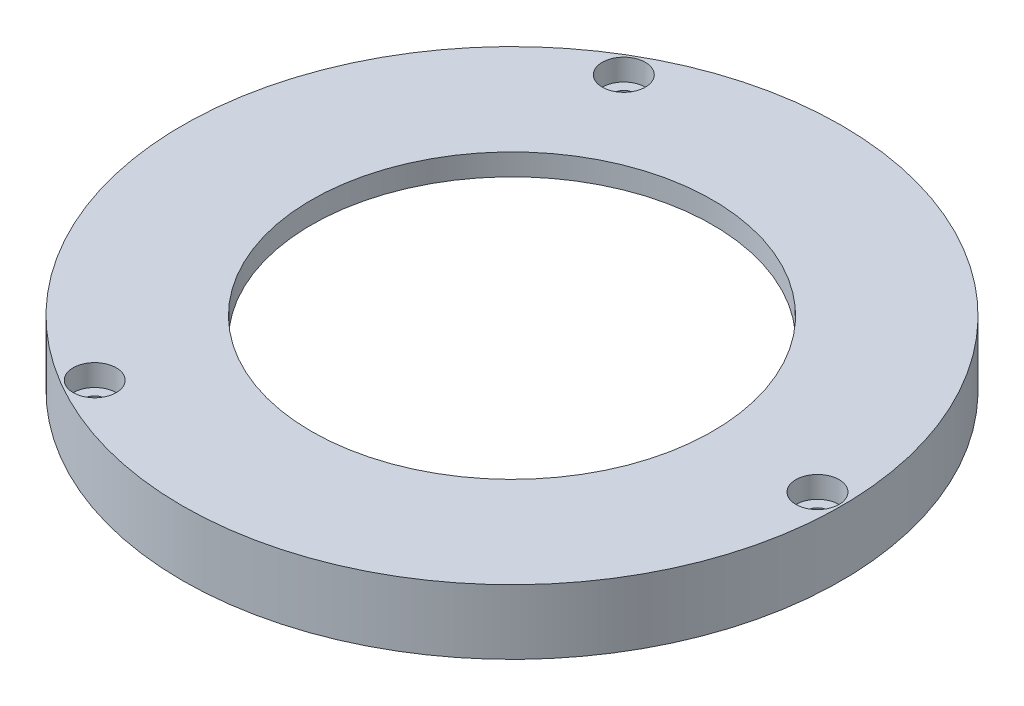
SolidWorks part; units mm, degrees
ref_plane "Front Plane" through (0, 0, 0) normal (0, 0, 1) x (1, 0, 0)
ref_plane "Top Plane" through (0, 0, 0) normal (0, 1, 0) x (1, 0, 0)
ref_plane "Right Plane" through (0, 0, 0) normal (1, 0, 0) x (0, 0, -1)
sketch "Sketch1" plane through (0, 0, 0) normal (0, 1, 0) x (1, 0, 0)
  line L0 (0, 0) -> (42.5, 0) construction
  circle A0 centre (0, 0) radius 45.85
  circle A1 centre (0, 0) radius 27.9
  circle A2 centre (42.5, 0) radius 1.5635
  circle A3 centre (-21.25, -36.8061) radius 1.5635
  circle A4 centre (-21.25, 36.8061) radius 1.5635
  circle A5 centre (0, 0) radius 39.3
  point P13 (0, 0)
  dimension "D1" = 91.7
  dimension "D2" = 55.8
  dimension "D4" = 3.127
  dimension "D6" = 78.6
  dimension "D3" = 42.5
  dimension "D5" = 3
extrude "Boss-Extrude1" add sketch "Sketch1" against normal blind 6 contours A0 A5 A2 A4 A3 region at (-44.5532, 0, 0)
extrude "Boss-Extrude2" add sketch "Sketch1<4>" along normal blind 3 contours A1 A5 | A0 A5 A2 A4 A3 region at (-44.5532, 0, 0) region at (-38.1884, 0, 0)
sketch "Sketch1<4>" plane through (0, 0, 0) normal (0, 1, 0) x (1, 0, 0) same geometry as "Sketch1"
sketch "Sketch2" plane through (0, 3, 0) normal (0, 1, 0) x (1, 0, 0)
  circle A0 centre (42.5, 0) radius 3
  circle A1 centre (-21.25, -36.8061) radius 3
  circle A2 centre (-21.25, 36.8061) radius 3
  point P4 (-22.9723, 41.559)
  point P5 (0, 0)
  point P9 (0, 0)
  dimension "D1" = 6
  dimension "D2" = 3
extrude "Cut-Extrude1" cut sketch "Sketch2" against normal blind 3
equation "\"bearing_21_OD\"= 21mm"
equation "\"pin_cirlce_diameter\"= 75mm"
equation "\"pin_diam\"= 6mm"
equation "\"gear_thickness\"= 4mm"
equation "\"ball_bearing_diam\"= 2.96mm"
equation "\"bearing_21_outer_clearance\"= 0.127mm'change this"
equation "\"bearing_15_OD\"= 15mm"
equation "\"bearing_15_outer_clearance\"= 0mm'change this"
equation "\"thrust_bearing_thickness\"= 5mm'measure this irl and change"
equation "\"D1@Boss-Extrude1\"=\"thrust_bearing_thickness\"+1mm"
